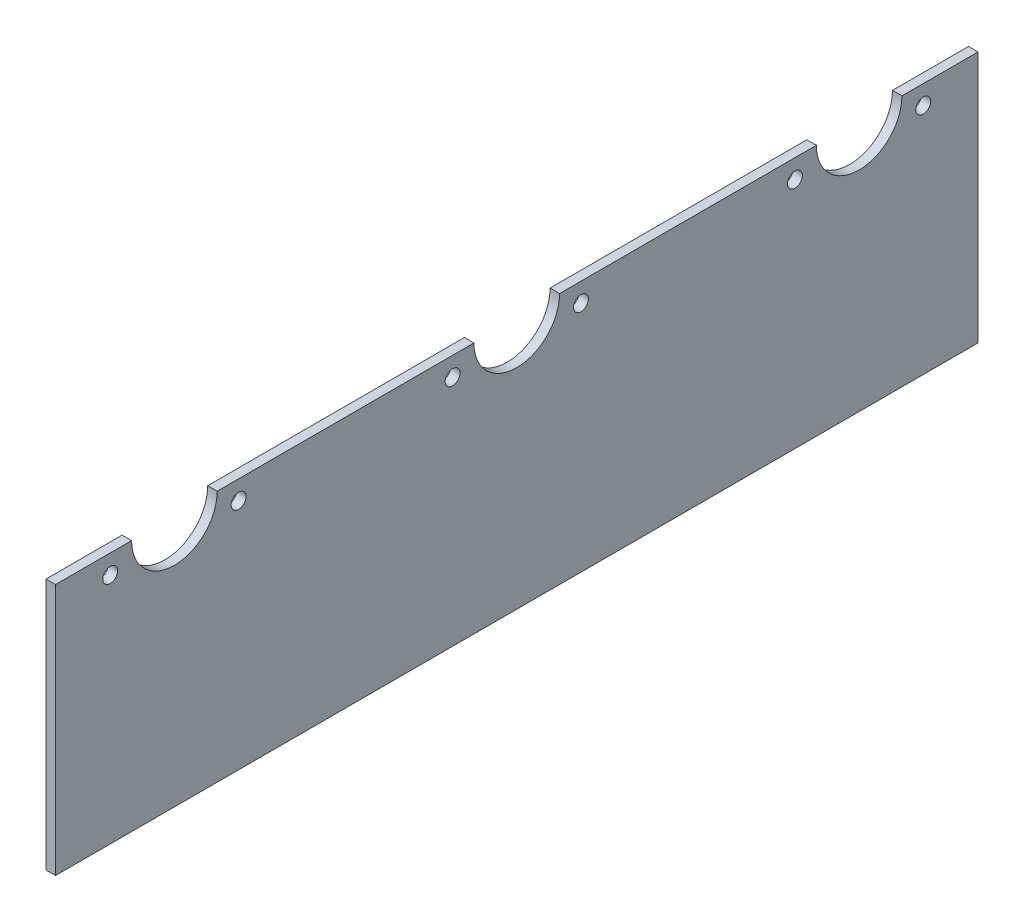
SolidWorks part; units mm, degrees
material "6061 Alloy"
ref_plane "Front Plane" through (0, 0, 0) normal (0, 0, 1) x (1, 0, 0)
ref_plane "Top Plane" through (0, 0, 0) normal (0, 1, 0) x (1, 0, 0)
ref_plane "Right Plane" through (0, 0, 0) normal (1, 0, 0) x (0, 0, -1)
sketch "Sketch1" plane through (0, 0, 0) normal (1, 0, 0) x (0, 0, -1)
  line L0 (153.9875, 0) -> (-153.9875, 0)
  line L1 (-153.9875, 0) -> (-153.9875, 84.1375)
  line L2 (-153.9875, 84.1375) -> (-128.5875, 84.1375)
  line L3 (-100.0125, 84.1375) -> (-14.2875, 84.1375)
  line L4 (14.2875, 84.1375) -> (100.0125, 84.1375)
  line L5 (128.5875, 84.1375) -> (153.9875, 84.1375)
  line L6 (153.9875, 84.1375) -> (153.9875, 0)
  line L7 (-153.9875, 25.4) -> (153.9875, 25.4) construction
  arc A6 (-128.5875, 84.1375) -> (-100.0125, 84.1375) centre (-114.3, 84.1375) ccw
  arc A7 (-14.2875, 84.1375) -> (14.2875, 84.1375) centre (0, 84.1375) ccw
  arc A8 (100.0125, 84.1375) -> (128.5875, 84.1375) centre (114.3, 84.1375) ccw
  point P4 (0, 0)
  dimension "D1" = 25.4
  dimension "D3" = 25.4
  dimension "D5" = 28.575
  dimension "D6" = 44.45
  dimension "D2" = 307.975
  dimension "D4" = 114.3
extrude "Boss-Extrude1" add sketch "Sketch1" along normal blind 3.175
hole_wizard "#10 Clearance Hole1" positions "Sketch2" profile "Sketch3" hole size "#10" standard "ANSI Inch" end condition through all
sketch "Sketch2" plane through (3.175, 0, 0) normal (1, 0, 0) x (0, 0, -1)
  line L0 (-135.7312, 77.7875) -> (-92.8687, 77.7875) construction
  line L2 (-21.4313, 77.7875) -> (21.4312, 77.7875) construction
  line L4 (92.8688, 77.7875) -> (135.7313, 77.7875) construction
  line L6 (-128.5875, 84.1375) -> (-153.9875, 84.1375) construction
  line L7 (-114.3, 77.7875) -> (-114.3, 84.1375) construction
  line L9 (0, 84.1375) -> (0, 77.7875) construction
  line L11 (114.3, 84.1375) -> (114.3, 77.7875) construction
  point P0 (-135.7312, 77.7875)
  point P2 (-92.8687, 77.7875)
  point P4 (-21.4313, 77.7875)
  point P6 (21.4312, 77.7875)
  point P8 (92.8688, 77.7875)
  point P10 (135.7313, 77.7875)
  dimension "D1" = 42.8625
  dimension "D2" = 6.35
sketch "Sketch3" plane through (3.175, 77.7875, 135.7312) normal (0, 1, 0) x (0, 0, -1)
  line L0 (0, 0) -> (0, 3.175)
  line L1 (0, 3.175) -> (2.4892, 3.175)
  line L2 (2.4892, 3.175) -> (2.4892, 0)
  line L5 (2.4892, 0) -> (0, 0)
  line L11 (0, -6.35) -> (0, 107.95) construction
  dimension "Thru Hole Dia." = 4.9784
  dimension "Thru Hole Depth" = 3.175
